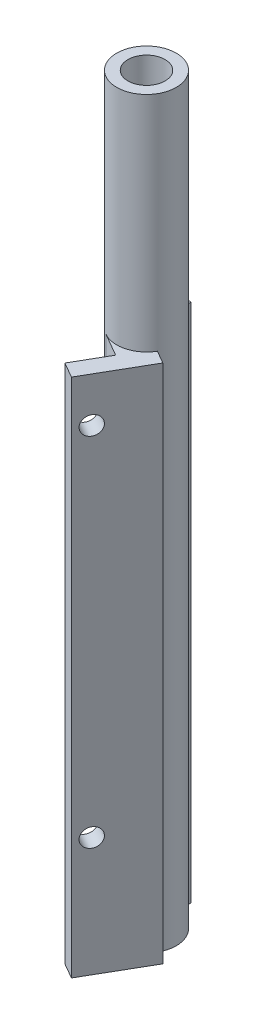
SolidWorks part; units mm, degrees
ref_plane "Front Plane" through (0, 0, 0) normal (0, 0, 1) x (1, 0, 0)
ref_plane "Top Plane" through (0, 0, 0) normal (0, 1, 0) x (1, 0, 0)
ref_plane "Right Plane" through (0, 0, 0) normal (1, 0, 0) x (0, 0, -1)
sketch "Sketch1" plane through (0, 0, 0) normal (0, 1, 0) x (1, 0, 0)
  circle A0 centre (0, 0) radius 5.08
  dimension "D1" = 10.16
extrude "Boss-Extrude1" add sketch "Sketch1" along normal blind 127
sketch "Sketch2" plane through (0, 0, 0) normal (0, -1, 0) x (1, 0, 0)
  circle A0 centre (0, 0) radius 3.175
  dimension "D1" = 6.35
extrude "Cut-Extrude1" cut sketch "Sketch2" against normal through all
sketch "Sketch3" plane through (0, 0, 0) normal (0, -1, 0) x (1, 0, 0)
  line L0 (0, 0) -> (0, -5.08) construction
  line L1 (0, -5.08) -> (-5.08, -5.08) construction
  line L2 (0, 0) -> (-2.54, 4.3994) construction
  line L3 (0, 0) -> (-5.08, 0) construction
  line L4 (-2.54, 4.3994) -> (1.8594, 6.9394) construction
  line L5 (8.7988, -5.08) -> (-1.3156, 12.4387) construction
  line L7 (0, -5.08) -> (-11.43, -5.08) construction
  line L8 (-1.3156, 12.4387) -> (-5.715, 9.8987)
  line L9 (-11.43, -5.08) -> (-11.43, 0)
  line L10 (-5.715, 9.8987) -> (-2.54, 4.3994)
  line L11 (-11.43, 0) -> (-5.08, 0)
  line L13 (-11.43, -5.08) -> (-11.43, -10.16)
  line L14 (-11.43, -10.16) -> (0, -10.16)
  line L15 (0, -10.16) -> (0, -5.08)
  line L17 (4.3994, 2.54) -> (8.7988, 5.08)
  line L18 (8.7988, 5.08) -> (3.0838, 14.9787)
  line L19 (3.0838, 14.9787) -> (-1.3156, 12.4387)
  arc A0 (-5.08, 0) -> (-2.54, 4.3994) centre (-0.899, 0.519) ccw
  circle A1 centre (0, 0) radius 3.175 construction
  circle A2 centre (0, 0) radius 5.08 construction
  arc A3 (4.3994, 2.54) -> (0, -5.08) centre (0, 0) cw
  point P9 (0, -5.08)
  dimension "D1" = 60
  dimension "D2" = 6.35
  dimension "D3" = 6.35
  dimension "D4" = 5.08
  dimension "D5" = 5.08
extrude "Boss-Extrude2" add sketch "Sketch3" against normal blind 88.9
sketch "Sketch4" plane through (0, 0, 0) normal (0, 0, 1) x (1, 0, 0)
  line L1 (-5.08, 88.9) -> (-5.08, 0) construction
  line L2 (-5.08, 88.9) -> (-11.43, 88.9) construction
  circle A0 centre (-8.89, 81.28) radius 1.5875
  circle A1 centre (-8.89, 20.32) radius 1.5875
  point P4 (0, 0)
  dimension "D3" = 3.175
  dimension "D1" = 7.62
  dimension "D2" = 68.58
  dimension "D4" = 3.81
extrude "Cut-Extrude2" cut sketch "Sketch4" against normal up to next
sketch "Sketch7" plane through (0, 0, 0) normal (0.866, 0, 0.5) x (0.5, 0, -0.866)
  line L1 (-5.08, 88.9) -> (-5.08, 0) construction
  line L3 (-2.54, 88.9) -> (-5.715, 88.9) construction
  line L5 (0, 88.9) -> (-11.43, 88.9) construction
  circle A0 centre (-8.89, 81.28) radius 1.5875
  circle A1 centre (-8.89, 20.32) radius 1.5875
  point P4 (0, 0)
  point P5 (0, 0)
  point P6 (0, 0)
  point P11 (0, 0)
  dimension "D2" = 3.175
  dimension "D1" = 3.81
  dimension "D3" = 7.62
  dimension "D4" = 68.58
extrude "Cut-Extrude6" cut sketch "Sketch7" along normal up to next
sketch "Sketch8" plane through (0, 0, 0) normal (0, -1, 0) x (1, 0, 0)
  line L0 (-5.715, 9.8987) -> (-1.7555, 12.1847)
  line L1 (3.0838, 14.9787) -> (-5.715, 9.8987) construction
  line L2 (-11.43, 0) -> (-11.43, -4.572)
  line L3 (-11.43, 0) -> (-11.43, -10.16) construction
  line L4 (-5.715, 9.8987) -> (-2.54, 4.3994)
  line L5 (-11.43, 0) -> (-5.08, 0)
  line L6 (-1.7555, 12.1847) -> (1.4195, 6.6854)
  line L7 (1.4195, 6.6854) -> (-2.54, 4.3994)
  line L8 (-11.43, -4.572) -> (-5.08, -4.572)
  line L9 (-5.08, -4.572) -> (-5.08, 0)
  dimension "D1" = 4.572
extrude "Cut-Extrude7" cut sketch "Sketch8" against normal up to next
sketch "Sketch9" plane through (0, 0, -10.16) normal (0, 0, -1) x (-1, 0, 0)
  line L1 (11.43, 88.9) -> (0, 88.9)
  line L2 (11.43, 88.9) -> (11.43, 0)
  line L3 (11.43, 0) -> (0, 0)
  line L4 (0, 88.9) -> (0, 0)
extrude "Cut-Extrude8" cut sketch "Sketch9" against normal blind 2.54
sketch "Sketch10" plane through (8.7988, 0, 5.08) normal (0.866, 0, 0.5) x (0.5, 0, -0.866)
  line L1 (-11.43, 0) -> (0, 0)
  line L2 (-11.43, 0) -> (-11.43, 88.9)
  line L3 (-11.43, 88.9) -> (0, 88.9)
  line L4 (0, 0) -> (0, 88.9)
extrude "Cut-Extrude9" cut sketch "Sketch10" against normal blind 2.54
